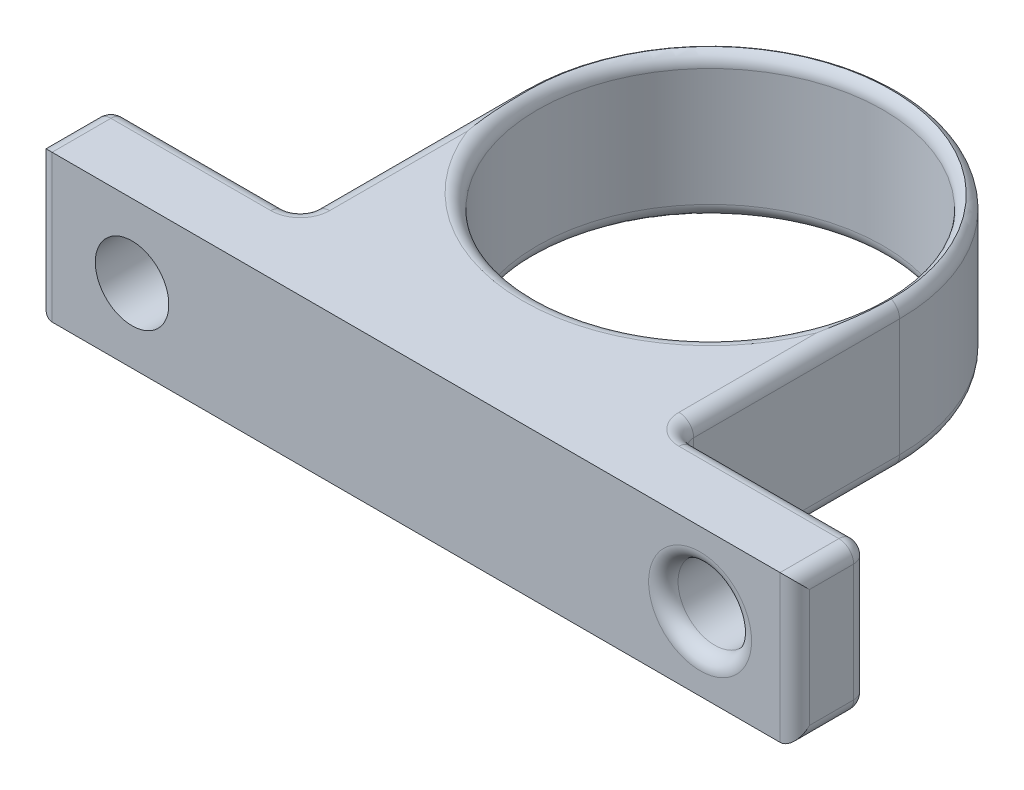
SolidWorks part; units mm, degrees
ref_plane "Front Plane" through (0, 0, 0) normal (0, 0, 1) x (1, 0, 0)
ref_plane "Top Plane" through (0, 0, 0) normal (0, 1, 0) x (1, 0, 0)
ref_plane "Right Plane" through (0, 0, 0) normal (1, 0, 0) x (0, 0, -1)
sketch "Sketch1" plane through (0, 0, 0) normal (0, 1, 0) x (1, 0, 0)
  circle A0 centre (0, 0) radius 25.75
  dimension "D1" = 51.5
extrude "Boss-Extrude1" add sketch "Sketch1" along normal blind 20
sketch "Sketch3" plane through (0, 20, 0) normal (0, 1, 0) x (1, 0, 0)
  line L1 (-25.75, 0) -> (25.75, 0)
  line L2 (-25.75, 0) -> (-25.75, -30)
  line L3 (-25.75, -30) -> (25.75, -30)
  line L4 (25.75, 0) -> (25.75, -30)
  circle A0 centre (0, 0) radius 25.75 construction
  dimension "D1" = 30
  dimension "D2" = 51.5
extrude "Boss-Extrude2" add sketch "Sketch3" against normal blind 20 contours L2 L3 L4 L1
sketch "Sketch2" plane through (0, 20, 0) normal (0, 1, 0) x (1, 0, 0)
  circle A0 centre (0, 0) radius 23.5
  dimension "D1" = 47
extrude "Cut-Extrude1" cut sketch "Sketch2" against normal blind 20
sketch "Sketch6" plane through (0, 0, 30) normal (0, 0, 1) x (1, 0, 0)
  line L1 (0, 0) -> (-51.5, 0)
  line L2 (0, 0) -> (0, 20)
  line L3 (0, 20) -> (-51.5, 20)
  line L4 (-51.5, 0) -> (-51.5, 20)
  dimension "D1" = 20
  dimension "D2" = 51.5
extrude "Boss-Extrude3" add sketch "Sketch6" along normal blind 10
pattern_linear "LPattern1" count 2 spacing 51.5 along (1, 0, 0) of "Boss-Extrude3"
sketch "Sketch7" plane through (0, 0, 30) normal (0, 0, -1) x (-1, 0, 0)
  line L0 (-51.5, 10) -> (-25.75, 10) construction
  line L1 (-51.5, 0) -> (-51.5, 20) construction
  line L2 (-25.75, 0) -> (-25.75, 20) construction
  line L3 (-38.625, 0) -> (-38.625, 20) construction
  line L4 (-25.75, 0) -> (-51.5, 0) construction
  line L5 (-51.5, 20) -> (-25.75, 20) construction
  circle A0 centre (-38.625, 10) radius 5
  dimension "D1" = 10
extrude "Cut-Extrude2" cut sketch "Sketch7" against normal blind 10
pattern_linear "LPattern2" count 2 spacing 77.25 along (-1, 0, 0) of "Cut-Extrude2"
fillet "Fillet3" radius 2 25 edges at (-51.5, 20, 35) (-51.5, 10, 40) (-51.5, 0, 35) (-51.5, 10, 30) (33.625, 10, 30) (33.625, 10, 40) (51.5, 0, 35) (51.5, 10, 40) (51.5, 20, 35) (51.5, 10, 30) (38.625, 20, 30) (25.75, 10, 30) (38.625, 0, 30) (-25.75, 10, 30) (-43.625, 10, 30) (-38.625, 20, 30) (-38.625, 0, 30) (-25.75, 0, 15) (0, 0, -25.75) (25.75, 0, 15) (-25.75, 20, 15) (0, 20, -25.75) (25.75, 20, 15) (0, 20, 23.5) (0, 0, 23.5)
sketch "Sketch8" [suppressed] plane through (0, 20, 0) normal (0, 1, 0) x (1, 0, 0)
  line L0 (49.5, -40) -> (-49.5, -40) construction
  line L1 (0, -40) -> (-7.8467, -40)
  line L2 (0, -40) -> (0, 0)
  line L3 (0, 0) -> (-7.8467, 0)
  line L4 (-7.8467, -40) -> (-7.8467, 0)
extrude "Cut-Extrude3" [suppressed] cut sketch "Sketch8" against normal blind 10
sketch "Sketch9" [suppressed] plane through (0, 20, 0) normal (0, 1, 0) x (1, 0, 0)
  line L1 (0, -40) -> (8.6904, -40)
  line L2 (0, -40) -> (0, 0)
  line L3 (0, 0) -> (8.6904, 0)
  line L4 (8.6904, -40) -> (8.6904, 0)
extrude "Cut-Extrude4" [suppressed] cut sketch "Sketch9" against normal blind 10 contours L2 L3 L4 L1
